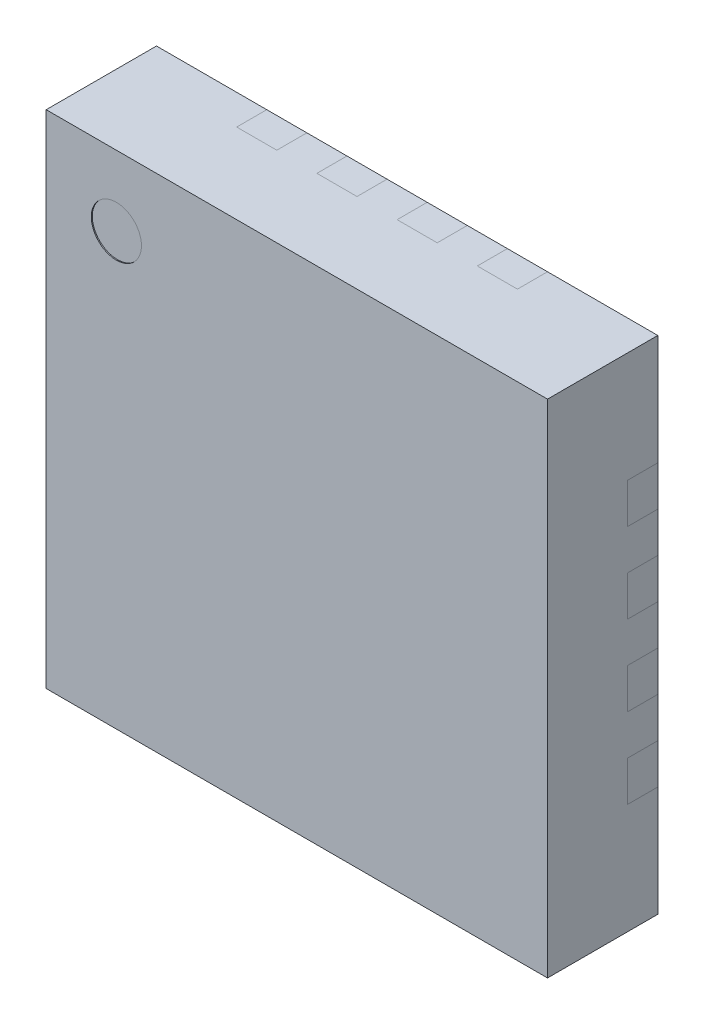
SolidWorks part; units mm, degrees
ref_plane "Front Plane" through (0, 0, 0) normal (0, 0, 1) x (1, 0, 0)
ref_plane "Top Plane" through (0, 0, 0) normal (0, 1, 0) x (1, 0, 0)
ref_plane "Right Plane" through (0, 0, 0) normal (1, 0, 0) x (0, 0, -1)
sketch "Sketch1" plane through (0, 0, 0) normal (0, 0, 1) x (1, 0, 0)
  line L1 (1.25, 1.25) -> (-1.25, 1.25)
  line L2 (1.25, 1.25) -> (1.25, -1.25)
  line L3 (1.25, -1.25) -> (-1.25, -1.25)
  line L4 (-1.25, 1.25) -> (-1.25, -1.25)
  line L5 (1.25, 1.25) -> (-1.25, -1.25) construction
  line L6 (1.25, -1.25) -> (-1.25, 1.25) construction
  point P0 (0, 0)
  dimension "D1" = 2.5
  dimension "D2" = 2.5
extrude "Boss-Extrude1" add sketch "Sketch1" along normal blind 0.55
sketch "Sketch2" plane through (0, -1.25, 0) normal (0, -1, 0) x (1, 0, 0)
  line L0 (0, 0.55) -> (0, 0) construction
  line L1 (-1.25, 0.55) -> (1.25, 0.55) construction
  line L2 (-1.25, 0) -> (1.25, 0) construction
  line L3 (-0.3, 0.15) -> (-0.1, 0.15)
  line L4 (-0.3, 0.15) -> (-0.3, -0.15)
  line L5 (-0.3, -0.15) -> (-0.1, -0.15)
  line L6 (-0.1, 0.15) -> (-0.1, -0.15)
  line L7 (-0.3, 0.15) -> (-0.1, -0.15) construction
  line L8 (-0.3, -0.15) -> (-0.1, 0.15) construction
  line L9 (0.1, 0.15) -> (0.3, 0.15)
  line L10 (0.1, 0.15) -> (0.1, -0.15)
  line L11 (0.1, -0.15) -> (0.3, -0.15)
  line L12 (0.3, 0.15) -> (0.3, -0.15)
  line L13 (0.5, 0.15) -> (0.7, 0.15)
  line L14 (0.5, 0.15) -> (0.5, -0.15)
  line L15 (0.5, -0.15) -> (0.7, -0.15)
  line L16 (0.7, 0.15) -> (0.7, -0.15)
  line L17 (-0.3, 0.15) -> (-0.1, 0.15)
  line L18 (-0.3, 0.15) -> (-0.3, -0.15)
  line L19 (-0.3, -0.15) -> (-0.1, -0.15)
  line L20 (-0.1, 0.15) -> (-0.1, -0.15)
  line L21 (0.1, 0.15) -> (0.3, 0.15)
  line L22 (0.1, 0.15) -> (0.1, -0.15)
  line L23 (0.1, -0.15) -> (0.3, -0.15)
  line L24 (0.3, 0.15) -> (0.3, -0.15)
  line L25 (-0.7, 0.15) -> (-0.5, 0.15)
  line L26 (-0.7, 0.15) -> (-0.7, -0.15)
  line L27 (-0.7, -0.15) -> (-0.5, -0.15)
  line L28 (-0.5, 0.15) -> (-0.5, -0.15)
  point P5 (-0.2, 0)
  line M3 (-1.25, 0) -> (1.25, 0)
  dimension "D1" = 0.2
  dimension "D2" = 0.15
  dimension "D3" = 0.2
  dimension "D4" = 3
  dimension "D5" = 2
extrude "Cut-Extrude1" cut sketch "Sketch2" against normal blind 0.4 contours L16 L14 L15 M3 | L16 L13 L14 M3 | L12 L10 L11 M3 | L12 L9 L10 M3 | L6 L3 L4 M3 | L6 L4 L5 M3 | L28 L25 L26 M3 | L28 L26 L27 M3 region at (0.6, -1.25, 0.075) region at (0.6, -1.25, -0.075) region at (0.2, -1.25, 0.075) region at (0.2, -1.25, -0.075) region at (-0.6, -1.25, -0.075) region at (-0.6, -1.25, 0.075) region at (-0.2, -1.25, 0.075) region at (-0.2, -1.25, -0.075)
ref_plane "Plane1" through (0, 0, 0) normal (0, -1, 0) x (-1, 0, 0)
ref_plane "Plane2" through (0, 0, 0) normal (-1, 0, 0) x (0, 0, 1)
ref_axis "Axis1" through (0, 0, 0.5775) along (0, 0, -1)
pattern_circular "CirPattern1" count 4 every 90 about axis through (0, 0, 0.5775) along (0, 0, -1) of "Cut-Extrude1"
sketch "Sketch3" plane through (0, 0, 0.15) normal (0, 0, -1) x (-1, 0, 0)
  line L0 (-0.7, -1.25) -> (-0.5, -1.25) construction
  line L1 (-0.5, -1.25) -> (-0.5, -0.85) construction
  line L2 (-0.5, -0.85) -> (-0.7, -0.85) construction
  line L3 (-0.7, -0.85) -> (-0.7, -1.25) construction
  line L4 (-0.3, -1.25) -> (-0.1, -1.25) construction
  line L5 (-0.1, -1.25) -> (-0.1, -0.85) construction
  line L6 (-0.1, -0.85) -> (-0.3, -0.85) construction
  line L7 (-0.3, -0.85) -> (-0.3, -1.25) construction
  line L8 (0.1, -1.25) -> (0.3, -1.25) construction
  line L9 (0.3, -1.25) -> (0.3, -0.85) construction
  line L10 (0.3, -0.85) -> (0.1, -0.85) construction
  line L11 (0.1, -0.85) -> (0.1, -1.25) construction
  line L12 (0.5, -1.25) -> (0.7, -1.25) construction
  line L13 (0.7, -1.25) -> (0.7, -0.85) construction
  line L14 (0.7, -0.85) -> (0.5, -0.85) construction
  line L15 (0.5, -0.85) -> (0.5, -1.25) construction
  line L16 (1.25, -0.7) -> (1.25, -0.5) construction
  line L17 (1.25, -0.5) -> (0.85, -0.5) construction
  line L18 (0.85, -0.5) -> (0.85, -0.7) construction
  line L19 (0.85, -0.7) -> (1.25, -0.7) construction
  line L20 (1.25, -0.3) -> (1.25, -0.1) construction
  line L21 (1.25, -0.1) -> (0.85, -0.1) construction
  line L22 (0.85, -0.1) -> (0.85, -0.3) construction
  line L23 (0.85, -0.3) -> (1.25, -0.3) construction
  line L24 (1.25, 0.1) -> (1.25, 0.3) construction
  line L25 (1.25, 0.3) -> (0.85, 0.3) construction
  line L26 (0.85, 0.3) -> (0.85, 0.1) construction
  line L27 (0.85, 0.1) -> (1.25, 0.1) construction
  line L28 (1.25, 0.5) -> (1.25, 0.7) construction
  line L29 (1.25, 0.7) -> (0.85, 0.7) construction
  line L30 (0.85, 0.7) -> (0.85, 0.5) construction
  line L31 (0.85, 0.5) -> (1.25, 0.5) construction
  line L32 (0.7, 1.25) -> (0.5, 1.25) construction
  line L33 (0.5, 1.25) -> (0.5, 0.85) construction
  line L34 (0.5, 0.85) -> (0.7, 0.85) construction
  line L35 (0.7, 0.85) -> (0.7, 1.25) construction
  line L36 (0.3, 1.25) -> (0.1, 1.25) construction
  line L37 (0.1, 1.25) -> (0.1, 0.85) construction
  line L38 (0.1, 0.85) -> (0.3, 0.85) construction
  line L39 (0.3, 0.85) -> (0.3, 1.25) construction
  line L40 (-0.1, 1.25) -> (-0.3, 1.25) construction
  line L41 (-0.3, 1.25) -> (-0.3, 0.85) construction
  line L42 (-0.3, 0.85) -> (-0.1, 0.85) construction
  line L43 (-0.1, 0.85) -> (-0.1, 1.25) construction
  line L44 (-0.5, 1.25) -> (-0.7, 1.25) construction
  line L45 (-0.7, 1.25) -> (-0.7, 0.85) construction
  line L46 (-0.7, 0.85) -> (-0.5, 0.85) construction
  line L47 (-0.5, 0.85) -> (-0.5, 1.25) construction
  line L48 (-1.25, 0.7) -> (-1.25, 0.5) construction
  line L49 (-1.25, 0.5) -> (-0.85, 0.5) construction
  line L50 (-0.85, 0.5) -> (-0.85, 0.7) construction
  line L51 (-0.85, 0.7) -> (-1.25, 0.7) construction
  line L52 (-1.25, 0.3) -> (-1.25, 0.1) construction
  line L53 (-1.25, 0.1) -> (-0.85, 0.1) construction
  line L54 (-0.85, 0.1) -> (-0.85, 0.3) construction
  line L55 (-0.85, 0.3) -> (-1.25, 0.3) construction
  line L56 (-1.25, -0.1) -> (-1.25, -0.3) construction
  line L57 (-1.25, -0.3) -> (-0.85, -0.3) construction
  line L58 (-0.85, -0.3) -> (-0.85, -0.1) construction
  line L59 (-0.85, -0.1) -> (-1.25, -0.1) construction
  line L60 (-1.25, -0.5) -> (-1.25, -0.7) construction
  line L61 (-1.25, -0.7) -> (-0.85, -0.7) construction
  line L62 (-0.85, -0.7) -> (-0.85, -0.5) construction
  line L63 (-0.85, -0.5) -> (-1.25, -0.5) construction
  line L64 (-0.7, -1.25) -> (-0.5, -1.25)
  line L65 (-0.5, -1.25) -> (-0.5, -0.85)
  line L66 (-0.5, -0.85) -> (-0.7, -0.85)
  line L67 (-0.7, -0.85) -> (-0.7, -1.25)
  line L68 (-0.3, -1.25) -> (-0.1, -1.25)
  line L69 (-0.1, -1.25) -> (-0.1, -0.85)
  line L70 (-0.1, -0.85) -> (-0.3, -0.85)
  line L71 (-0.3, -0.85) -> (-0.3, -1.25)
  line L72 (0.1, -1.25) -> (0.3, -1.25)
  line L73 (0.3, -1.25) -> (0.3, -0.85)
  line L74 (0.3, -0.85) -> (0.1, -0.85)
  line L75 (0.1, -0.85) -> (0.1, -1.25)
  line L76 (0.5, -1.25) -> (0.7, -1.25)
  line L77 (0.7, -1.25) -> (0.7, -0.85)
  line L78 (0.7, -0.85) -> (0.5, -0.85)
  line L79 (0.5, -0.85) -> (0.5, -1.25)
  line L80 (1.25, -0.7) -> (1.25, -0.5)
  line L81 (1.25, -0.5) -> (0.85, -0.5)
  line L82 (0.85, -0.5) -> (0.85, -0.7)
  line L83 (0.85, -0.7) -> (1.25, -0.7)
  line L84 (1.25, -0.3) -> (1.25, -0.1)
  line L85 (1.25, -0.1) -> (0.85, -0.1)
  line L86 (0.85, -0.1) -> (0.85, -0.3)
  line L87 (0.85, -0.3) -> (1.25, -0.3)
  line L88 (1.25, 0.1) -> (1.25, 0.3)
  line L89 (1.25, 0.3) -> (0.85, 0.3)
  line L90 (0.85, 0.3) -> (0.85, 0.1)
  line L91 (0.85, 0.1) -> (1.25, 0.1)
  line L92 (1.25, 0.5) -> (1.25, 0.7)
  line L93 (1.25, 0.7) -> (0.85, 0.7)
  line L94 (0.85, 0.7) -> (0.85, 0.5)
  line L95 (0.85, 0.5) -> (1.25, 0.5)
  line L96 (0.7, 1.25) -> (0.5, 1.25)
  line L97 (0.5, 1.25) -> (0.5, 0.85)
  line L98 (0.5, 0.85) -> (0.7, 0.85)
  line L99 (0.7, 0.85) -> (0.7, 1.25)
  line L100 (0.3, 1.25) -> (0.1, 1.25)
  line L101 (0.1, 1.25) -> (0.1, 0.85)
  line L102 (0.1, 0.85) -> (0.3, 0.85)
  line L103 (0.3, 0.85) -> (0.3, 1.25)
  line L104 (-0.1, 1.25) -> (-0.3, 1.25)
  line L105 (-0.3, 1.25) -> (-0.3, 0.85)
  line L106 (-0.3, 0.85) -> (-0.1, 0.85)
  line L107 (-0.1, 0.85) -> (-0.1, 1.25)
  line L108 (-0.5, 1.25) -> (-0.7, 1.25)
  line L109 (-0.7, 1.25) -> (-0.7, 0.85)
  line L110 (-0.7, 0.85) -> (-0.5, 0.85)
  line L111 (-0.5, 0.85) -> (-0.5, 1.25)
  line L112 (-1.25, 0.7) -> (-1.25, 0.5)
  line L113 (-1.25, 0.5) -> (-0.85, 0.5)
  line L114 (-0.85, 0.5) -> (-0.85, 0.7)
  line L115 (-0.85, 0.7) -> (-1.25, 0.7)
  line L116 (-1.25, 0.3) -> (-1.25, 0.1)
  line L117 (-1.25, 0.1) -> (-0.85, 0.1)
  line L118 (-0.85, 0.1) -> (-0.85, 0.3)
  line L119 (-0.85, 0.3) -> (-1.25, 0.3)
  line L120 (-1.25, -0.1) -> (-1.25, -0.3)
  line L121 (-1.25, -0.3) -> (-0.85, -0.3)
  line L122 (-0.85, -0.3) -> (-0.85, -0.1)
  line L123 (-0.85, -0.1) -> (-1.25, -0.1)
  line L124 (-1.25, -0.5) -> (-1.25, -0.7)
  line L125 (-1.25, -0.7) -> (-0.85, -0.7)
  line L126 (-0.85, -0.7) -> (-0.85, -0.5)
  line L127 (-0.85, -0.5) -> (-1.25, -0.5)
extrude "Boss-Extrude2" add sketch "Sketch3" along normal up to surface (0.15 mm away) separate body up to face at (0, 0, 0)
sketch "Sketch4" plane through (0, 0, 0.55) normal (0, 0, 1) x (1, 0, 0)
  line L0 (1.25, 1.25) -> (-1.25, 1.25) construction
  line L1 (-1.25, 1.25) -> (-1.25, -1.25) construction
  circle A0 centre (-0.9, 0.9) radius 0.125
  dimension "D3" = 0.25
  dimension "D1" = 0.35
  dimension "D2" = 0.35
extrude "Cut-Extrude2" cut sketch "Sketch4" against normal blind 0.005
